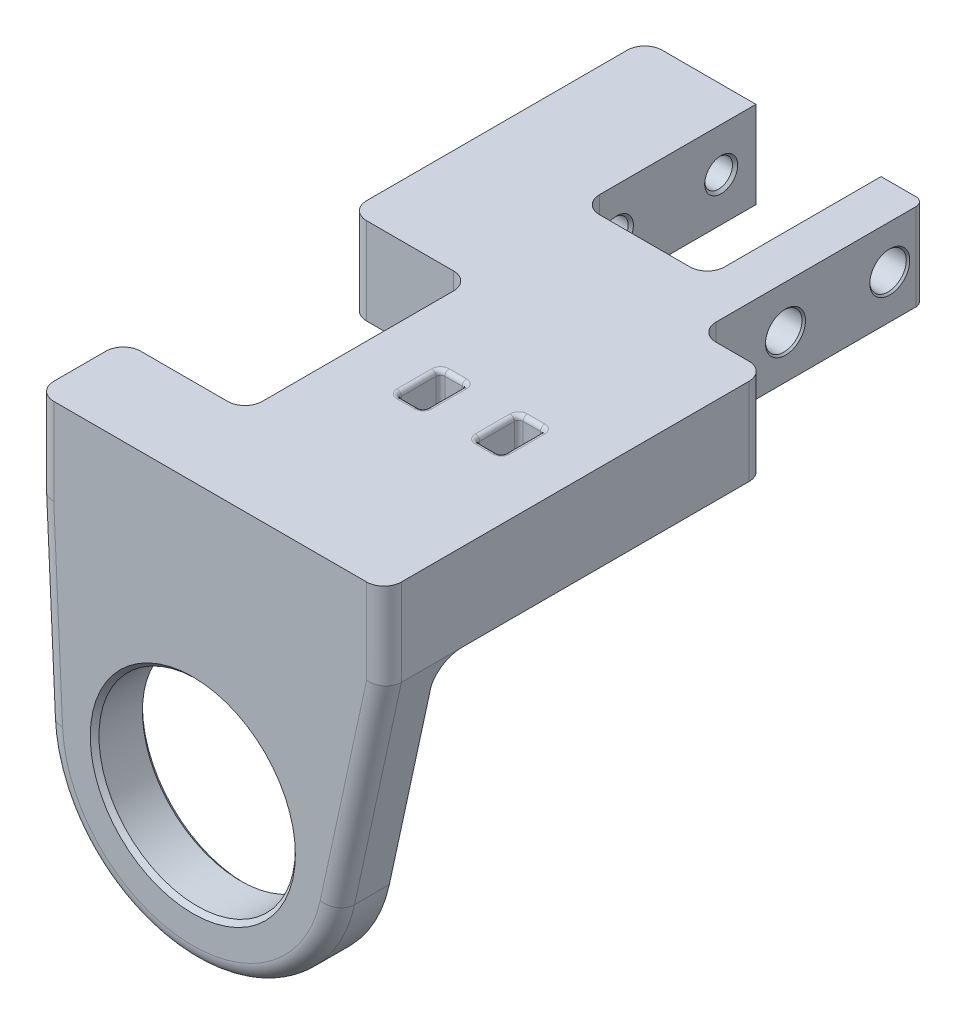
SolidWorks part; units mm, degrees
ref_plane "Top Plane" through (0, 0, 0) normal (0, 0, 1) x (1, 0, 0)
ref_plane "Right Plane" through (0, 0, 0) normal (0, 1, 0) x (1, 0, 0)
ref_plane "Front Plane" through (0, 0, 0) normal (1, 0, 0) x (0, 0, -1)
sketch "Sketch1" plane through (0, 0, 0) normal (0, 0, 1) x (1, 0, 0)
  line L0 (0, 0) -> (0, 31.25) construction
  line L1 (22, 31.25) -> (22, 21.25)
  line L2 (-18, 31.25) -> (22, 31.25)
  line L3 (-18, 31.25) -> (-18, 21.25)
  line L4 (22, 21.25) -> (16.6143, -3.6007)
  line L5 (-18, 21.25) -> (-16.9819, -0.7847)
  line L6 (-18, 21.25) -> (22, 21.25) construction
  arc A0 (-16.9819, -0.7847) -> (16.6143, -3.6007) centre (0, 0) ccw construction
  circle A1 centre (0, 0) radius 11 construction
  circle A2 centre (0, 0) radius 4 construction
  arc A3 (-16.9819, -0.7847) -> (16.6143, -3.6007) centre (0, 0) ccw
  dimension "D1" = 34
  dimension "D2" = 22
  dimension "D3" = 8
  dimension "D6" = 10
  dimension "D4" = 21.25
  dimension "D5" = 40
  dimension "D7" = 18
extrude "Boss-Extrude1" add sketch "Sketch1" along normal blind 6
sketch "Sketch2" plane through (0, 0, 6) normal (0, 0, 1) x (1, 0, 0)
  circle A2 centre (0, 0) radius 11.3
  circle A3 centre (0, 0) radius 11.3
  dimension "D1" = 0.3
extrude "Cut-Extrude1" cut sketch "Sketch2" against normal through all
sketch "Sketch3" plane through (0, 0, 0) normal (0, 0, -1) x (-1, 0, 0)
  line L0 (18, 31.25) -> (-22, 31.25) construction
  line L1 (-22, 31.25) -> (-9, 31.25) construction
  line L2 (-22, 31.25) -> (-22, 21.25) construction
  line L3 (-22, 21.25) -> (-9, 21.25) construction
  line L4 (-9, 31.25) -> (-9, 21.25) construction
  line L5 (5, 31.25) -> (18, 31.25) construction
  line L6 (5, 31.25) -> (5, 21.25) construction
  line L7 (5, 21.25) -> (18, 21.25) construction
  line L8 (18, 31.25) -> (18, 21.25) construction
  line L9 (-9, 26.25) -> (5, 26.25) construction
  line L11 (-2, 26.25) -> (-2, 31.25) construction
  line L13 (-22, 31.25) -> (18, 31.25)
  line L14 (-22, 31.25) -> (-22, 21.25)
  line L15 (-22, 21.25) -> (18, 21.25)
  line L16 (18, 31.25) -> (18, 21.25)
  point P12 (-2, 26.25)
  dimension "D1" = 14
extrude "Boss-Extrude2" add sketch "Sketch3" along normal blind 44
sketch "Sketch4" plane through (0, 0, -44) normal (0, 0, -1) x (-1, 0, 0)
  line L0 (-22, 21.25) -> (18, 21.25) construction
  line L1 (-22, 31.25) -> (-9.2, 31.25)
  line L2 (-22, 31.25) -> (-22, 21.25)
  line L3 (-22, 21.25) -> (-9.2, 21.25)
  line L4 (-9.2, 31.25) -> (-9.2, 21.25)
  line L5 (5.2, 31.25) -> (18, 31.25)
  line L6 (5.2, 31.25) -> (5.2, 21.25)
  line L7 (5.2, 21.25) -> (18, 21.25)
  line L8 (18, 31.25) -> (18, 21.25)
  line L9 (-9, 31.25) -> (-9, 21.25) construction
  line L10 (5, 31.25) -> (5, 21.25) construction
  line L11 (18, 31.25) -> (-22, 31.25) construction
  dimension "D1" = 0.2
  dimension "D2" = 0.2
extrude "Boss-Extrude3" add sketch "Sketch4" along normal blind 20
fillet "Fillet1" radius 3 1 edges at (2, 21.25, 0)
sketch "Sketch5" plane through (9.2, 0, 0) normal (-1, 0, 0) x (0, 0, 1)
  line L0 (-64, 26.25) -> (-44, 26.25) construction
  line L1 (-64, 21.25) -> (-64, 31.25) construction
  line L2 (-44, 21.25) -> (-44, 31.25) construction
  line L3 (-54, 31.25) -> (-54, 26.25) construction
  line L4 (-64, 31.25) -> (-44, 31.25) construction
  circle A0 centre (-60, 26.25) radius 1.75
  circle A1 centre (-48, 26.25) radius 1.75
  dimension "D1" = 3.5
  dimension "D2" = 12
hole_wizard "CBORE for M3 Hex Socket Head Cap Screw1" positions "Sketch6" profile "Sketch7" counterbore size "M3" standard "ISO" end condition through all
sketch "Sketch6" plane through (-18, 0, 0) normal (-1, 0, 0) x (0, 0, 1)
  point P0 (-60, 26.25)
  point P3 (-48, 26.25)
sketch "Sketch7" plane through (-18, 26.25, -60) normal (0, 1, 0) x (0, 0, 1)
  line L0 (0, 0) -> (0, 40)
  line L1 (0, 40) -> (1.6, 40)
  line L3 (1.6, 40) -> (1.6, 3.4)
  line L4 (1.6, 3.4) -> (3.25, 3.4)
  line L5 (3.25, 3.4) -> (3.25, 0)
  line L7 (3.25, 0) -> (0, 0)
  line L11 (0, -6.35) -> (0, 107.95) construction
  dimension "Thru Hole Dia." = 3.2
  dimension "Thru Hole Depth" = 40
  dimension "C'Bore Dia." = 6.5
  dimension "C'Bore Depth" = 3.4
sketch "Sketch8" plane through (22, 0, 0) normal (1, 0, 0) x (0, 0, -1)
  line L1 (49.7321, 29.25) -> (46.2679, 29.25)
  line L2 (46.2679, 29.25) -> (44.5359, 26.25)
  line L3 (44.5359, 26.25) -> (46.2679, 23.25)
  line L4 (46.2679, 23.25) -> (49.7321, 23.25)
  line L5 (49.7321, 23.25) -> (51.4641, 26.25)
  line L6 (51.4641, 26.25) -> (49.7321, 29.25)
  line L7 (58.2679, 29.25) -> (56.5359, 26.25)
  line L8 (56.5359, 26.25) -> (58.2679, 23.25)
  line L9 (58.2679, 23.25) -> (61.7321, 23.25)
  line L10 (61.7321, 23.25) -> (63.4641, 26.25)
  line L11 (63.4641, 26.25) -> (61.7321, 29.25)
  line L12 (61.7321, 29.25) -> (58.2679, 29.25)
  circle A0 centre (48, 26.25) radius 3 construction
  circle A1 centre (60, 26.25) radius 3 construction
  dimension "D1" = 6
extrude "Cut-Extrude3" [suppressed] cut sketch "Sketch8" against normal offset from surface (10.8 mm away) 2 up to face at (9.2, 27.85, -60)
sketch "Sketch9" plane through (0, 31.25, 0) normal (0, 1, 0) x (1, 0, 0)
  line L0 (-18, -6) -> (-18, 64) construction
  line L1 (-18, 30) -> (-4, 30)
  line L2 (-18, 30) -> (-18, 4)
  line L3 (-18, 4) -> (-4, 4)
  line L4 (-4, 30) -> (-4, 4)
  line L5 (22, -6) -> (-18, -6) construction
  dimension "D1" = 36
  dimension "D2" = 10
  dimension "D3" = 14
extrude "Cut-Extrude4" cut sketch "Sketch9" against normal through all
sketch "Sketch10" plane through (0, 31.25, 0) normal (0, 1, 0) x (1, 0, 0)
  line L0 (9, 23.4892) -> (9, 10.5108) construction
  line L1 (3, 19.5) -> (6, 19.5)
  line L2 (3, 19.5) -> (3, 14.5)
  line L3 (3, 14.5) -> (6, 14.5)
  line L4 (6, 19.5) -> (6, 14.5)
  line L5 (12, 19.5) -> (12, 14.5)
  line L6 (15, 14.5) -> (12, 14.5)
  line L7 (15, 19.5) -> (15, 14.5)
  line L8 (15, 19.5) -> (12, 19.5)
  line L9 (3, 17) -> (15, 17) construction
  line L10 (-4, 17) -> (9, 17) construction
  line L11 (-4, 4) -> (-4, 30) construction
  line L12 (-4, 10.5108) -> (22, 10.5108) construction
  line L13 (22, -6) -> (22, 64) construction
  point P10 (9, 17)
  dimension "D1" = 3
  dimension "D2" = 5
  dimension "D3" = 6
extrude "Cut-Extrude5" cut sketch "Sketch10" against normal up to next
sketch "Sketch11" plane through (0, 31.25, 0) normal (0, 1, 0) x (1, 0, 0)
  line L0 (9.2, 64) -> (22, 64) construction
  line L1 (14.2, 64) -> (22, 64)
  line L2 (14.2, 64) -> (14.2, 38)
  line L3 (14.2, 38) -> (22, 38)
  line L4 (22, 64) -> (22, 38)
  line L5 (22, -6) -> (22, 64) construction
  line L7 (-4, 30) -> (-18, 30) construction
  line L8 (9.2, 64) -> (9.2, 44) construction
  dimension "D1" = 8
  dimension "D2" = 5
extrude "Cut-Extrude6" cut sketch "Sketch11" against normal through all
fillet "Fillet2" radius 2 2 edges at (-4, 26.25, -4) (-4, 26.25, -30)
fillet "Fillet3" radius 2 2 edges at (9.2, 26.25, -44) (-5.2, 26.25, -44)
fillet "Fillet4" [suppressed] radius 2
fillet "Fillet7" radius 2 10 edges at (22, 26.25, -38) (22, 26.25, 6) (-18, 26.25, 6) (-18, 26.25, -4) (-18, 26.25, -30) (-18, 26.25, -64) (14.2, 26.25, -38) (-17.4909, 10.2327, 6) (19.3072, 8.8247, 6) (-1.42, -16.9406, 6)
fillet "Fillet8" radius 1 1 edges at (14.2, 26.25, -64)
fillet "Fillet5" [suppressed] radius 2
chamfer "Chamfer1" distance 0.5 angle 45 2 edges at (11.3, 0, 6) (11.3, 0, 0)
fillet "Fillet6" radius 0.5 24 edges at (13.5, 21.25, -14.5) (13.5, 31.25, -14.5) (13.5, 31.25, -19.5) (13.5, 21.25, -19.5) (4.5, 21.25, -14.5) (4.5, 31.25, -14.5) (4.5, 31.25, -19.5) (4.5, 21.25, -19.5) (15, 26.25, -19.5) (15, 31.25, -17) (15, 26.25, -14.5) (15, 21.25, -17) (12, 26.25, -14.5) (12, 31.25, -17) (12, 26.25, -19.5) (12, 21.25, -17) (6, 26.25, -19.5) (6, 31.25, -17) (6, 26.25, -14.5) (6, 21.25, -17) (3, 26.25, -14.5) (3, 31.25, -17) (3, 26.25, -19.5) (3, 21.25, -17)
sketch "Sketch12" plane through (14.2, 0, 0) normal (1, 0, 0) x (0, 0, -1)
  circle A0 centre (48, 26.25) radius 2.1
  circle A1 centre (60, 26.25) radius 2.1
  dimension "D1" = 4.2
extrude "Cut-Extrude7" cut sketch "Sketch12" against normal blind 4
chamfer "Chamfer3" distance 0.2 angle 45 2 edges at (14.2, 26.25, -62.1) (14.2, 26.25, -50.1)
chamfer "Chamfer2" distance 0.3 angle 45 6 edges at (-14.6, 26.25, -46.4) (-14.6, 26.25, -58.4) (-5.2, 24.65, -48) (-5.2, 24.65, -60) (9.2, 27.85, -48) (9.2, 27.85, -60)
